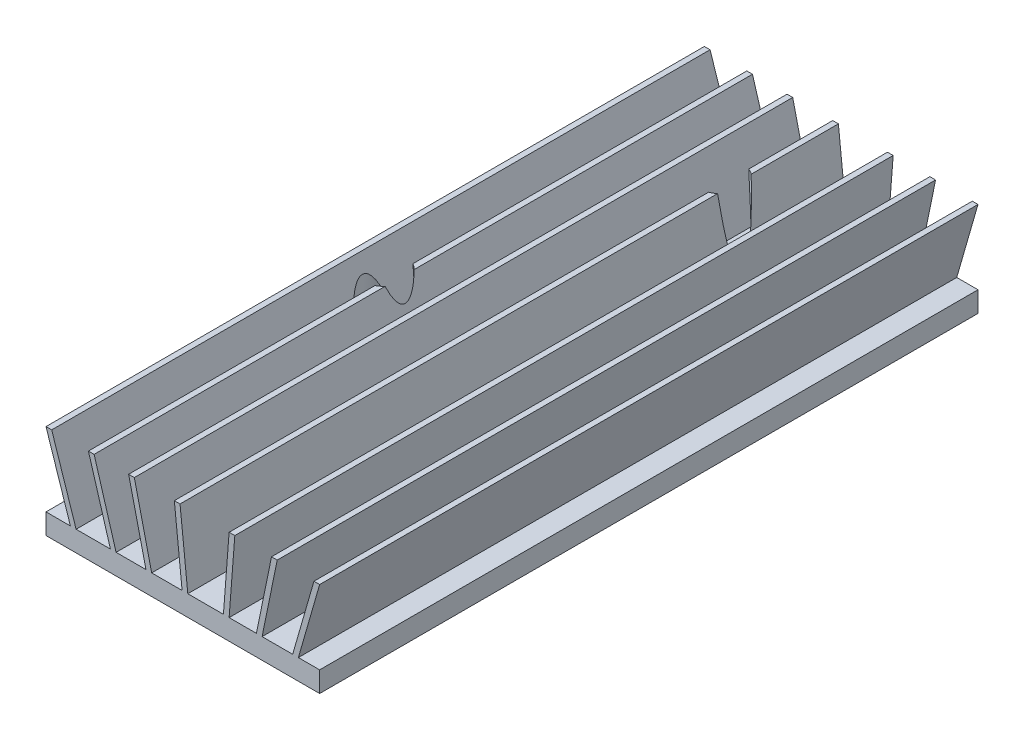
SolidWorks part; units mm, degrees
ref_plane "Front Plane" through (0, 0, 0) normal (0, 0, 1) x (1, 0, 0)
ref_plane "Top Plane" through (0, 0, 0) normal (0, 1, 0) x (1, 0, 0)
ref_plane "Right Plane" through (0, 0, 0) normal (1, 0, 0) x (0, 0, -1)
sketch "Sketch1" plane through (0, 0, 0) normal (0, 0, 1) x (1, 0, 0)
  line L1 (0, 0) -> (25.4, 0)
  line L2 (0, 0) -> (0, 1.905)
  line L3 (0, 1.905) -> (25.4, 1.905)
  line L4 (25.4, 0) -> (25.4, 1.905)
  dimension "D1" = 1.905
  dimension "D2" = 25.4
extrude "Base" add sketch "Sketch1" along normal blind 61.1124
sketch "Sketch2" plane through (0, 0, 0) normal (0, 0, -1) x (-1, 0, 0)
  line L0 (-23.4267, 1.905) -> (-25.4, 8.763)
  line L1 (-25.4, 8.763) -> (-24.8714, 8.763)
  line L2 (-24.8714, 8.763) -> (-22.8981, 1.905)
  line L3 (-25.4, 1.905) -> (0, 1.905) construction
  line L4 (-23.4267, 1.905) -> (-22.8981, 1.905)
  line L6 (-20.0581, 1.905) -> (-19.5295, 1.905)
  line L7 (-19.5295, 1.905) -> (-20.9344, 8.763)
  line L8 (-20.9344, 8.763) -> (-21.463, 8.763)
  line L9 (-21.463, 8.763) -> (-20.0581, 1.905)
  line L10 (-16.9974, 1.905) -> (-16.4688, 1.905)
  line L11 (0, 1.905) -> (0, 0) construction
  line L12 (-2.794, 1.905) -> (-2.2654, 1.905)
  line L13 (-2.2654, 1.905) -> (0, 8.763)
  line L14 (0, 8.763) -> (-0.5286, 8.763)
  line L15 (-0.5286, 8.763) -> (-2.794, 1.905)
  line L16 (-16.4688, 1.905) -> (-16.9974, 8.763)
  line L17 (-16.9974, 8.763) -> (-17.526, 8.763)
  line L18 (-17.526, 8.763) -> (-16.9974, 1.905)
  line L19 (-12.4412, 8.763) -> (-11.9126, 8.763)
  line L20 (-11.9126, 8.763) -> (-12.6334, 1.905)
  line L21 (-12.6334, 1.905) -> (-13.162, 1.905)
  line L22 (-13.162, 1.905) -> (-12.4412, 8.763)
  line L23 (-8.1994, 8.763) -> (-7.6708, 8.763)
  line L24 (-7.6708, 8.763) -> (-9.2806, 1.905)
  line L25 (-9.2806, 1.905) -> (-9.8092, 1.905)
  line L26 (-9.8092, 1.905) -> (-8.1994, 8.763)
  line L27 (-4.4656, 8.763) -> (-3.937, 8.763)
  line L28 (-3.937, 8.763) -> (-5.9786, 1.905)
  line L29 (-5.9786, 1.905) -> (-6.5072, 1.905)
  line L30 (-6.5072, 1.905) -> (-4.4656, 8.763)
  dimension "D1" = 0.508
  dimension "D2" = 6.858
  dimension "D3" = 2.5019
  dimension "D4" = 21.463
  dimension "D5" = 2.794
  dimension "D6" = 17.7927
  dimension "D7" = 14.732
  dimension "D8" = 17.526
  dimension "D9" = 10.8966
  dimension "D10" = 13.4874
  dimension "D11" = 7.5438
  dimension "D12" = 17.7292
  dimension "D13" = 4.2418
  dimension "D14" = 21.463
extrude "Fins" add sketch "Sketch2" against normal up to surface (61.1124 mm away) up to face at (12.7, 0.9525, 61.1124)
sketch "Sketch3" plane through (0, 1.905, 0) normal (0, 1, 0) x (1, 0, 0)
  line L4 (2.794, -61.1124) -> (5.9786, -61.1124)
  line L5 (5.9786, -61.1124) -> (5.9786, 0)
  line L6 (5.9786, 0) -> (2.794, 0)
  line L7 (2.794, 0) -> (2.794, -61.1124)
  line L8 (2.794, -61.1124) -> (5.9786, -61.1124)
  line L9 (5.9786, -61.1124) -> (5.9786, 0)
  line L10 (5.9786, 0) -> (2.794, 0)
  circle A0 centre (11.2, -9.655) radius 1.9939 construction
  circle A1 centre (11.2, -9.655) radius 1.9939
  circle A2 centre (3, -32.755) radius 1.9939 construction
  circle A3 centre (3, -32.755) radius 1.9939
  dimension "D1" = 0
extrude "Cut-Extrude1" cut sketch "Sketch3" against normal through all and the other way through all contours A1 | A3
